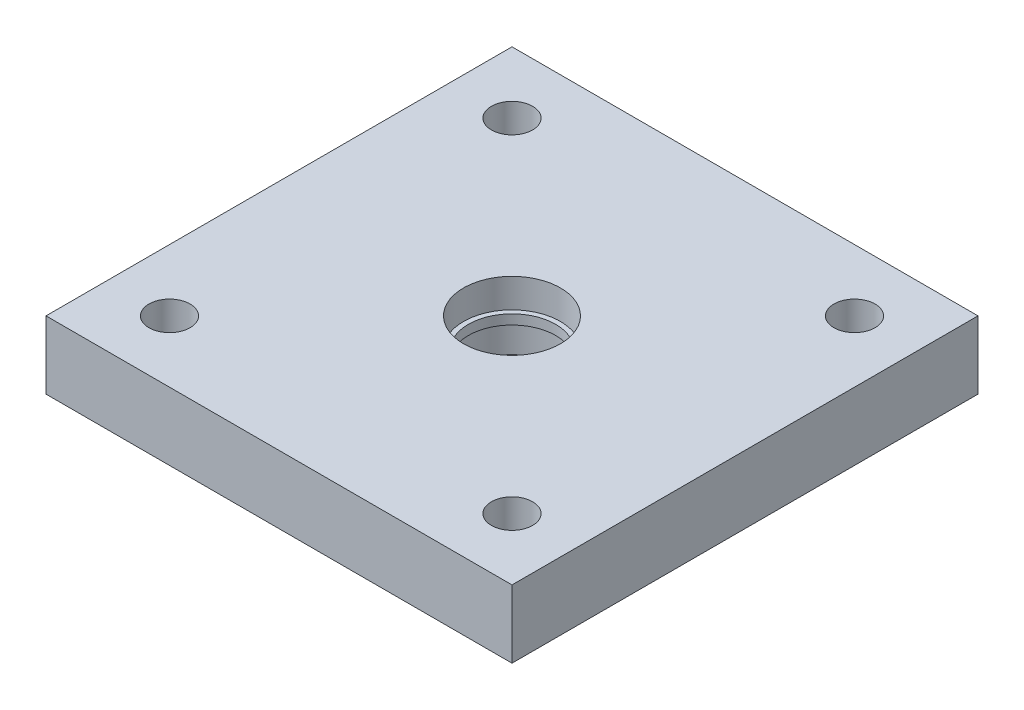
SolidWorks part; units mm, degrees
material "1060 Alloy"
ref_plane "Front" through (0, 0, 0) normal (0, 0, 1) x (1, 0, 0)
ref_plane "Top" through (0, 0, 0) normal (0, 1, 0) x (1, 0, 0)
ref_plane "Right" through (0, 0, 0) normal (1, 0, 0) x (0, 0, -1)
sketch "Sketch1" plane through (0, 0, 0) normal (0, 1, 0) x (1, 0, 0)
  line L1 (-48.1053, 48.1053) -> (48.1053, 48.1053)
  line L2 (-48.1053, 48.1053) -> (-48.1053, -48.1053)
  line L3 (-48.1053, -48.1053) -> (48.1053, -48.1053)
  line L4 (48.1053, 48.1053) -> (48.1053, -48.1053)
  line L5 (-48.1053, 48.1053) -> (48.1053, -48.1053) construction
  line L6 (-48.1053, -48.1053) -> (48.1053, 48.1053) construction
  circle A0 centre (-35.3553, 35.3553) radius 4.25
  circle A1 centre (35.3553, 35.3553) radius 4.25
  circle A2 centre (35.3553, -35.3553) radius 4.25
  circle A3 centre (-35.3553, -35.3553) radius 4.25
  circle A4 centre (0, 0) radius 9
  point P0 (0, 0)
  point P17 (0, 0)
  dimension "D3" = 8.5
  dimension "D7" = 18
  dimension "D2" = 50
  dimension "D5" = 50
  dimension "D6" = 50
  dimension "D1" = 12.75
  dimension "D4" = 4
extrude "body and main holes" add sketch "Sketch1" along normal blind 14
sketch "Sketch2" plane through (0, 14, 0) normal (0, 1, 0) x (1, 0, 0)
  circle A0 centre (0, 0) radius 10
  dimension "D1" = 20
extrude "seal hole" cut sketch "Sketch2" against normal blind 6
sketch "Sketch3" plane through (0, 0, 0) normal (0, -1, 0) x (1, 0, 0)
  circle A0 centre (0, 0) radius 10
  dimension "D1" = 20
extrude "bearing hole" cut sketch "Sketch3" against normal blind 6
sketch "Sketch4" plane through (0, 0, 0) normal (0, -1, 0) x (1, 0, 0)
  circle A0 centre (0, 0) radius 15 construction
  circle A1 centre (0, -15) radius 2
  circle A2 centre (-15, 0) radius 2
  circle A3 centre (0, 15) radius 2
  circle A4 centre (15, 0) radius 2
  point P14 (0, 0)
  dimension "D1" = 30
  dimension "D2" = 4
  dimension "D3" = 4
extrude "Cut-Extrude1" cut sketch "Sketch4" against normal blind 10
equation "\"motor mount pattern diameter\"= 30mm"
equation "\"D2@Sketch1\" = \"motor mount to housing m8 pattern diameter\" / 2"
equation "\"D3@Sketch1\" = \"motor mount to housing m8 screw hole diameter\""
equation "\"D5@Sketch1\" = \"motor mount to housing m8 pattern diameter\" / 2"
equation "\"D6@Sketch1\" = \"motor mount to housing m8 pattern diameter\" / 2"
equation "\"D1@Sketch1\" = \"motor mount to housing m8 screw post radius\""
equation "\"D1@body and main holes\" = \"housing base thickness\""
equation "\"D1@Sketch2\" = \"seal OD\""
equation "\"D1@seal hole\" = \"seal depth\""
equation "\"D1@Sketch3\" = \"bearing OD\""
equation "\"D1@bearing hole\" = \"bearing depth\""
equation "\"bearing OD\" = 20mm"
equation "\"bearing outer race thickness\"= 1mm"
equation "\"bearing ID\"= 10mm"
equation "\"bearing depth\"= 6mm"
equation "\"bearing inner race thickness\"= 1mm"
equation "\"seal OD\" = 20mm"
equation "\"seal ID\"= 8mm"
equation "\"seal depth\"= 6mm"
equation "\"impeller base outer diameter\"= 1.75in"
equation "\"impeller base outer thickness\"= 1mm"
equation "\"impeller base center thickness\"= 5mm"
equation "\"impeller number of vanes\"= 8"
equation "\"impeller vane outer height`\"= 4mm"
equation "\"impeller vane inner height\"= 8mm"
equation "\"impeller primary vane opening diamater\"= 10mm"
equation "\"impeller shaft bore size\"=4mm "
equation "\"impeller vane inner thickness\"= .75mm"
equation "\"impeller vane outer thickness\"= 1.5mm"
equation "\"impeller primary vane entrance angle\"= 20deg"
equation "\"impeller secondary vane entrance angle\"= 20deg"
equation "\"impeller secondary vane opening diameter\"= 10mm"
equation "\"motor to housing distance\"= 60mm"
equation "\"motor mount coupler shaft hole diameter\"= \"coupler shaft base diameter\"+ 4mm"
equation "\"motor mount to housing m8 screw hole diameter\"= 8.5mm"
equation "\"motor mount to housing m8 screw post radius\"= ( 3 * \"motor mount to housing m8 screw hole diameter\" ) / 2"
equation "\"motor mount to housing m8 pattern diameter\"= 100mm"
equation "\"motor mount to housing m4 screw hole diamater\"= 4mm"
equation "\"motor mount to housing m4 head diameter\"= 7.25mm"
equation "\"motor mount to housing m4 head depth\"= 4mm"
equation "\"motor mount plate thickness\"= 6mm + \"motor mount to housing m4 head depth\""
equation "\"coupler shaft set screw 1 distance\"= \"motor mount shaft hole depth\" / 3"
equation "\"coupler shaft set screw 2 distance\"= \"motor mount shaft hole depth\" * 4 / 5"
equation "\"housing bearing seat lip thickness\" = 2mm"
equation "\"housing base thickness\"= \"housing bearing seat lip thickness\" + \"seal depth\" + \"bearing depth\""
equation "\"housing top impeller vertical clearance\"= 1mm"
equation "\"housing top impeller horizontal clearance\"= 1mm"
equation "\"housing top impeller bottom clearance\"= 2mm"
equation "\"housing top impeller cavity height\"= \"housing top impeller bottom clearance\" + \"impeller base center thickness\" + \"impeller vane inner height\" + \"housing top impeller vertical clearance\""
equation "\"housing top impeller cavity diameter\"= 2 * \"housing top impeller horizontal clearance\" + \"impeller base outer diameter\""
equation "\"housing top impeller cavity tip height\"= \"housing top impeller bottom clearance\" + \"housing top impeller vertical clearance\" + \"impeller base outer thickness\" + \"impeller vane outer height\""
equation "\"housing top entrance OD\"= 20mm"
equation "\"housing top exit OD\"= 5mm"
equation "\"housing top o-ring channel height\"= 1.5mm"
equation "\"housing top o ring channel width\"= 1.5mm"
equation "\"housing top threaded inlet depth\"= 8mm"
equation "\"housing top total thickness\"= \"housing top threaded inlet depth\" + \"housing top impeller cavity height\""
equation "\"housing top total width\"= 10mm"
equation "\"housing top exit threaded diameter\"= 8mm"
equation "\"housing top exit threaded depth\"= 8mm"
equation "\"motor shaft pride\"= 32mm"
equation "\"motor shaft flat section length from tip\"= 25.7mm"
equation "\"motor shaft bore end clearance\"= 2mm"
equation "\"motor mount shaft hole depth\"= \"motor shaft pride\""
equation "\"coupler shaft set screw drill hole diameter\"= 6mm"
equation "\"coupler shaft motor shaft hole diameter\"= 8mm"
equation "\"coupler shaft base diameter\"= 18mm"
equation "\"coupler shaft base length\"= \"motor mount shaft hole depth\" + 10mm"
equation "\"coupler shaft second section diameter\"= \"bearing ID\" + \"bearing inner race thickness\" * 2"
equation "\"coupler shaft second section length\"= \"motor to housing distance\" -  \"coupler shaft base length\" - 2mm"
equation "\"coupler shaft third section diamater\"= \"bearing ID\""
equation "\"coupler shaft third section length\"= \"bearing depth\""
equation "\"coupler shaft seal section diameter\" = \"seal ID\""
equation "\"coupler shaft seal section length\" = \"housing base thickness\"+\"housing top impeller bottom clearance\"-\"bearing depth\""
equation "\"coupler shaft impeller section diameter\" = 6mm"
equation "\"coupler shaft impeller section length\" = \"impeller bolt surface height\"-.5mm"
equation "\"coupler shaft impeller screw hole diameter\" = \"motor mount to housing m4 screw hole diamater\""
equation "\"coupler shaft impeller screw hole depth\" = 10mm"
equation "\"D7@Sketch1\"=\"bearing OD\"-\"bearing outer race thickness\"*2"
equation "\"D1@Sketch4\"=\"bearing OD\"+ 10mm"
equation "\"D2@Sketch4\"=\"motor mount to housing m4 screw hole diamater\""
equation "\"D1@Cut-Extrude1\"=\"housing base thickness\"-4mm"
